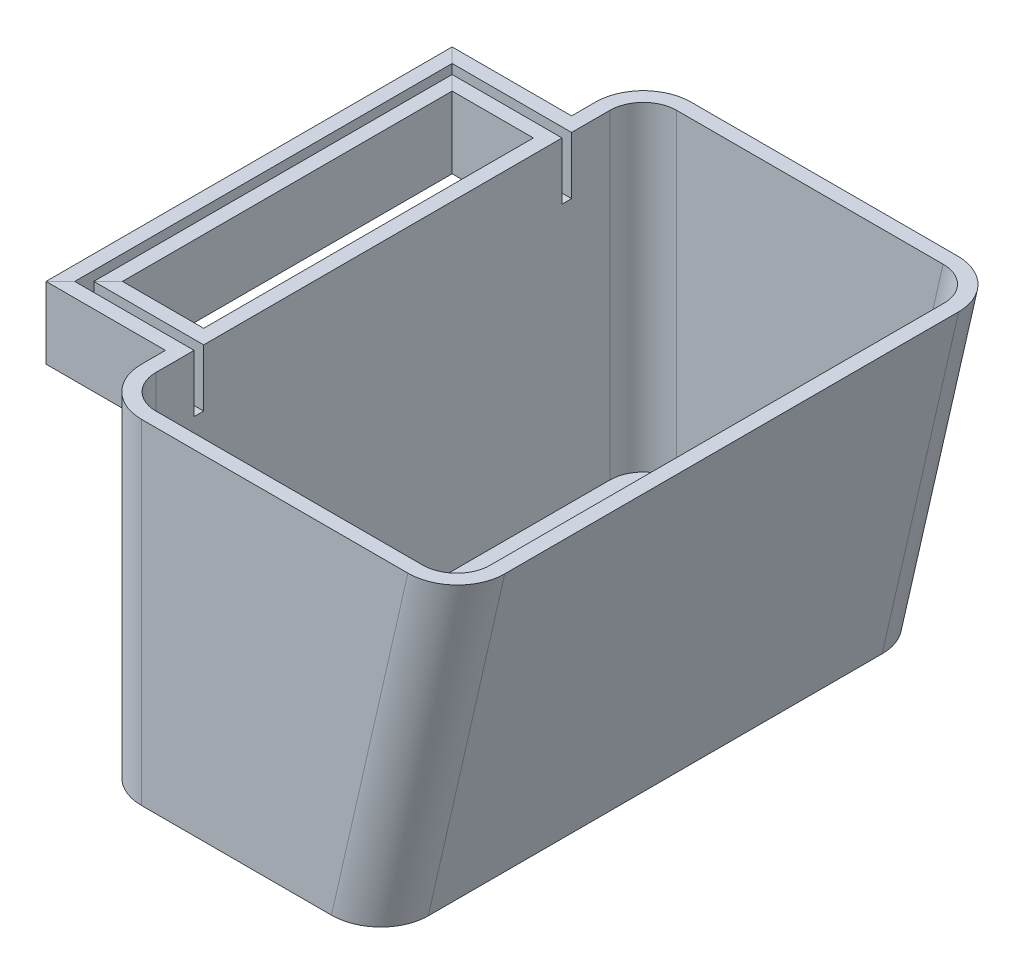
SolidWorks part; units mm, degrees
ref_plane "前视基准面" through (0, 0, 0) normal (0, 0, 1) x (1, 0, 0)
ref_plane "上视基准面" through (0, 0, 0) normal (0, 1, 0) x (1, 0, 0)
ref_plane "右视基准面" through (0, 0, 0) normal (1, 0, 0) x (0, 0, -1)
other "Configuration Table"
sketch "草图2" plane through (0, 0, 0) normal (0, 0, 1) x (1, 0, 0)
  line L0 (0, 0) -> (0, 70)
  line L1 (0, 70) -> (76, 70)
  line L2 (76, 70) -> (60, 0)
  line L3 (60, 0) -> (0, 0)
  dimension "D1" = 70
  dimension "D2" = 76
  dimension "D3" = 60
extrude "凸台-拉伸2" add sketch "草图2" along normal blind 115
sketch "草图4" plane through (0, 0, 0) normal (-1, 0, 0) x (0, 0, 1)
  line L0 (15, 70) -> (15, 55)
  line L1 (115, 70) -> (0, 70) construction
  line L2 (15, 55) -> (23, 55)
  line L3 (23, 55) -> (23, 70)
  line L4 (23, 70) -> (15, 70)
  dimension "D1" = 15
  dimension "D2" = 8
  dimension "D3" = 15
sketch "草图5" plane through (0, 70, 0) normal (0, 1, 0) x (1, 0, 0)
  line L0 (0, -15) -> (-25, -15)
  line L1 (0, -23) -> (0, -15) construction
  line L2 (0, -15) -> (0, -23) construction
  line L3 (-25, -15) -> (-25, -100)
  line L4 (-25, -100) -> (0, -100)
  line L5 (0, -115) -> (0, 0) construction
  dimension "D1" = 25
  dimension "D2" = 85
  dimension "D3" = 15
sweep "扫描1" add profiles "草图4" path "草图5"
fillet "圆角3" radius 10 1 edges at (0, 35, 115)
fillet "圆角4" radius 10 1 edges at (68, 35, 115)
fillet "圆角5" radius 10 2 edges at (0, 35, 0) (68, 35, 0)
shell "抽壳5" thickness 3 removed face at (-21, 70, 57.5) removed face at (13.7244, 70, 57.5)
